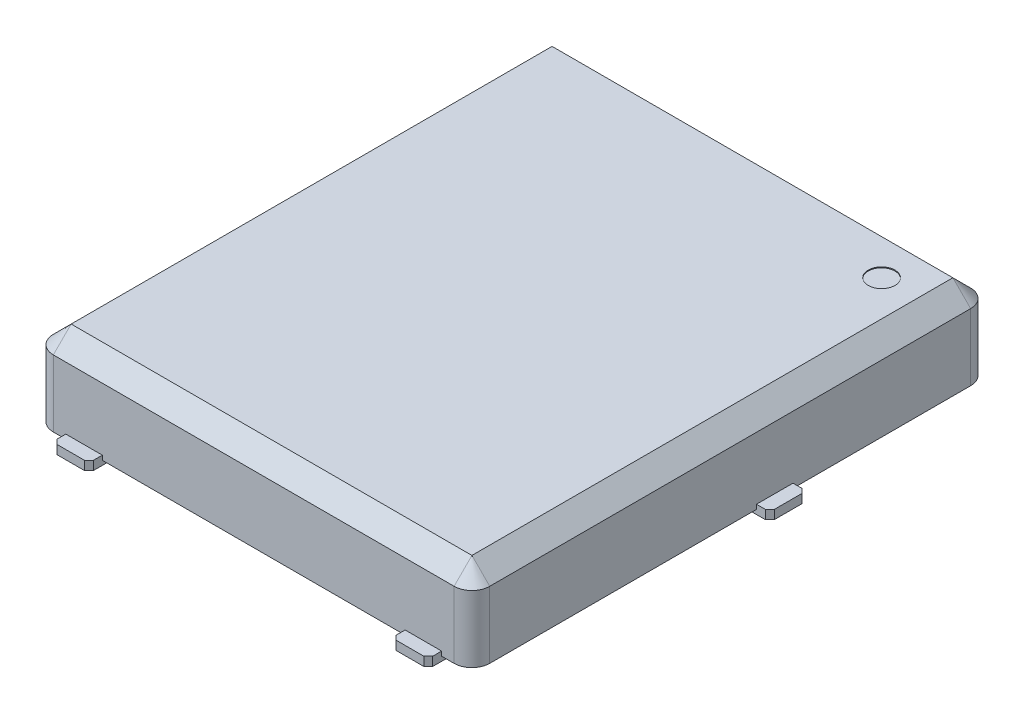
SolidWorks part; units mm, degrees
ref_plane "Спереди" through (0, 0, 0) normal (0, 0, 1) x (1, 0, 0)
ref_plane "Сверху" through (0, 0, 0) normal (0, 1, 0) x (1, 0, 0)
ref_plane "Справа" through (0, 0, 0) normal (1, 0, 0) x (0, 0, -1)
sketch "Эскиз1" plane through (0, 0, 0) normal (0, 1, 0) x (1, 0, 0)
  line L1 (-2.45, 2.9) -> (2.45, 2.9)
  line L2 (-2.45, 2.9) -> (-2.45, -2.9)
  line L3 (-2.45, -2.9) -> (2.45, -2.9)
  line L4 (2.45, 2.9) -> (2.45, -2.9)
  line L5 (-2.45, 2.9) -> (2.45, -2.9) construction
  line L6 (-2.45, -2.9) -> (2.45, 2.9) construction
  point P0 (0, 0)
  dimension "D1" = 5.8
  dimension "D2" = 4.9
extrude "Бобышка-Вытянуть1" add sketch "Эскиз1" along normal blind 0.95
fillet "Скругление1" radius 0.2 4 edges at (-2.45, 0.475, -2.9) (2.45, 0.475, -2.9) (-2.45, 0.475, 2.9) (2.45, 0.475, 2.9)
chamfer "Фаска1" distance 0.2 angle 45 8 edges at (2.45, 0.95, 0) (2.3914, 0.95, -2.8414) (2.3914, 0.95, 2.8414) (0, 0.95, -2.9) (0, 0.95, 2.9) (-2.3914, 0.95, -2.8414) (-2.3914, 0.95, 2.8414) (-2.45, 0.95, 0)
sketch "Эскиз2" plane through (0, 0, 0) normal (0, -1, 0) x (1, 0, 0)
  line L0 (0.84, -3.05) -> (0.84, -2.44)
  line L1 (2.11, -3.05) -> (1.7, -3.05)
  line L2 (2.11, -3.05) -> (2.11, -2.44)
  line L3 (2.11, -2.44) -> (1.7, -2.44)
  line L4 (1.7, -3.05) -> (1.7, -2.44)
  line L5 (2.11, -3.05) -> (1.7, -2.44) construction
  line L6 (2.11, -2.44) -> (1.7, -3.05) construction
  line L7 (0.84, -3.05) -> (0.43, -3.05)
  line L8 (0.43, -3.05) -> (0.43, -2.44)
  line L9 (0.84, -2.44) -> (0.43, -2.44)
  line L10 (-0.43, -3.05) -> (-0.43, -2.44)
  line L11 (-0.43, -3.05) -> (-0.84, -3.05)
  line L12 (-0.84, -3.05) -> (-0.84, -2.44)
  line L13 (-0.43, -2.44) -> (-0.84, -2.44)
  line L14 (-1.7, -3.05) -> (-1.7, -2.44)
  line L15 (-1.7, -3.05) -> (-2.11, -3.05)
  line L16 (-2.11, -3.05) -> (-2.11, -2.44)
  line L17 (-1.7, -2.44) -> (-2.11, -2.44)
  line L18 (0, 0) -> (0, -3.5933) construction
  line L19 (1.7, -2.44) -> (0, -2.44) construction
  line L20 (0, -2.44) -> (-1.7, -2.44) construction
  line L21 (2.25, -2.9) -> (-2.25, -2.9) construction
  point P0 (1.905, -2.745)
  dimension "D1" = 0.61
  dimension "D2" = 0.41
  dimension "D3" = 4
  dimension "D4" = 0.15
extrude "Бобышка-Вытянуть2" add sketch "Эскиз2" along normal blind 0.05 and the other way blind 0.05
chamfer "Фаска2" distance 0.05 angle 45 8 edges at (-2.11, 0, -3.05) (-1.7, 0, -3.05) (-0.84, 0, -3.05) (-0.43, 0, -3.05) (0.43, 0, -3.05) (0.84, 0, -3.05) (1.7, 0, -3.05) (2.11, 0, -3.05)
sketch "Эскиз3" plane through (0, 0, 0) normal (0, -1, 0) x (1, 0, 0)
  line L0 (0.43, -2.44) -> (0.84, -2.44) construction
  line L1 (2.075, -1.24) -> (-2.075, -1.24)
  line L2 (2.075, -1.24) -> (2.075, 2.61)
  line L3 (2.075, 2.61) -> (-2.075, 2.61)
  line L4 (-2.075, -1.24) -> (-2.075, 2.61)
  line L5 (2.075, -1.24) -> (-2.075, 2.61) construction
  line L6 (2.075, 2.61) -> (-2.075, -1.24) construction
  line L7 (-2.25, 2.9) -> (2.25, 2.9) construction
  line L9 (-2.6, -0.5) -> (-2.075, -0.5) construction
  line L10 (-2.075, -0.705) -> (-2.6, -0.705)
  line L11 (-2.075, -0.705) -> (-2.075, -0.295)
  line L12 (-2.075, -0.295) -> (-2.6, -0.295)
  line L13 (-2.6, -0.705) -> (-2.6, -0.295)
  line L14 (-2.45, -2.7) -> (-2.45, 2.7) construction
  line L15 (0, 0.685) -> (0, -0.8393) construction
  line L16 (2.075, -0.295) -> (2.6, -0.295)
  line L17 (2.6, -0.705) -> (2.6, -0.295)
  line L18 (2.075, -0.705) -> (2.6, -0.705)
  line L19 (2.075, -0.705) -> (2.075, -0.295)
  line L20 (-2.11, 2.61) -> (-1.7, 3.05) construction
  line L21 (2.11, 2.61) -> (1.7, 2.61)
  line L22 (2.11, 2.61) -> (2.11, 3.05)
  line L23 (2.11, 3.05) -> (1.7, 3.05)
  line L24 (1.7, 2.61) -> (1.7, 3.05)
  line L25 (2.11, 2.61) -> (1.7, 3.05) construction
  line L26 (2.11, 3.05) -> (1.7, 2.61) construction
  line L27 (-2.11, 3.05) -> (-1.7, 2.61) construction
  line L28 (-2.11, 3.05) -> (-1.7, 3.05)
  line L29 (-1.7, 2.61) -> (-1.7, 3.05)
  line L30 (-2.11, 2.61) -> (-1.7, 2.61)
  line L31 (-2.11, 2.61) -> (-2.11, 3.05)
  point P0 (0, 0.685)
  point P24 (1.905, 2.83)
  point P33 (-1.905, 2.83)
  line M33 (2.45, -2.7) -> (2.45, 2.7)
  line M35 (2.25, 2.9) -> (-2.25, 2.9)
  line M37 (-2.45, 2.7) -> (-2.45, -2.7)
  dimension "D1" = 1.2
  dimension "D2" = 3.85
  dimension "D3" = 4.15
  dimension "D4" = 3.4
  dimension "D5" = 0.41
  dimension "D6" = 0.15
  dimension "D7" = 3.81
  dimension "D8" = 0.41
  dimension "D9" = 0.15
extrude "Бобышка-Вытянуть3" add sketch "Эскиз3" along normal blind 0.05 and the other way blind 0.05 contours L4 L1 L2 L3 | L24 L22 L23 M35 | L24 L3 L21 L22 M35 | L31 L29 L28 M35 | L31 L30 L3 L29 M35 | L2 L18 L16 M33 | L18 L17 L16 M33 | L4 L12 L10 M37 | L13 L10 L12 M37 region at (0, 0, 0.685) region at (2.2625, 0, -0.5) region at (-2.2625, 0, -0.5) region at (2.525, 0, -0.5) region at (-2.525, 0, -0.5) region at (1.905, 0, 2.755) region at (-1.905, 0, 2.755) region at (1.905, 0, 2.975) region at (-1.905, 0, 2.975)
chamfer "Фаска3" distance 0.05 angle 45 12 edges at (1.7, -0.025, 2.61) (-1.7, -0.025, 2.61) (-2.11, -0.025, 2.61) (2.11, -0.025, 2.61) (2.11, 0, 3.05) (1.7, 0, 3.05) (-1.7, 0, 3.05) (-2.11, 0, 3.05) (-2.6, 0, -0.295) (-2.6, 0, -0.705) (2.6, 0, -0.295) (2.6, 0, -0.705)
sketch "Эскиз4" plane through (0, 0.95, 0) normal (0, 1, 0) x (1, 0, 0)
  line L0 (-2.25, 2.9) -> (2.25, 2.9) construction
  line L1 (2.45, 2.7) -> (2.45, -2.7) construction
  circle A0 centre (1.85, 2.3) radius 0.15
  point P2 (1.7168, 2.209)
  dimension "D1" = 0.3
  dimension "D2" = 0.6
  dimension "D3" = 0.6
extrude "Вырез-Вытянуть1" cut sketch "Эскиз4" against normal blind 0.01
